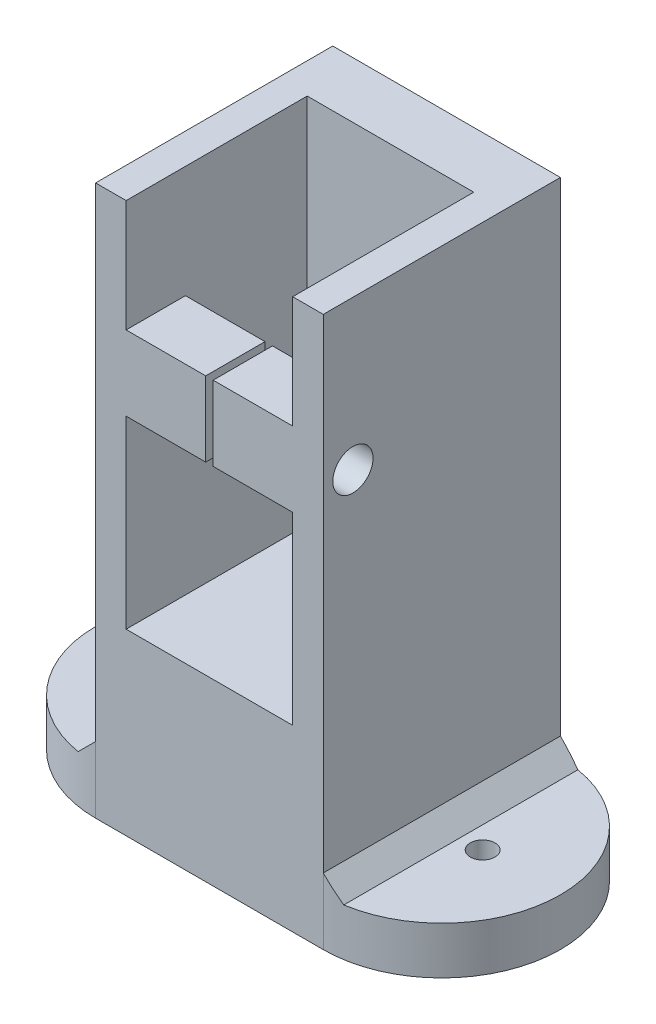
SolidWorks part; units mm, degrees
ref_plane "Front Plane" through (0, 0, 0) normal (0, 0, 1) x (1, 0, 0)
ref_plane "Top Plane" through (0, 0, 0) normal (0, 1, 0) x (1, 0, 0)
ref_plane "Right Plane" through (0, 0, 0) normal (1, 0, 0) x (0, 0, -1)
sketch "Sketch1" plane through (0, 0, 0) normal (0, 1, 0) x (1, 0, 0)
  line L0 (-5.461, 15.875) -> (35.941, 15.875) construction
  line L1 (0, 0) -> (30.48, 0)
  line L2 (0, 0) -> (0, 31.75)
  line L3 (0, 31.75) -> (30.48, 31.75)
  line L4 (30.48, 0) -> (30.48, 31.75)
  line L6 (15.24, 31.75) -> (15.24, 0) construction
  arc A0 (0, 0) -> (0, 31.75) centre (0, 15.875) cw
  arc A1 (30.48, 0) -> (30.48, 31.75) centre (30.48, 15.875) ccw
  circle A2 centre (35.941, 15.875) radius 1.651
  circle A3 centre (-5.461, 15.875) radius 1.651
  point P7 (15.24, 15.875)
  point P9 (15.24, 15.875)
  dimension "D1" = 30.48
  dimension "D3" = 3.302
  dimension "D2" = 31.75
  dimension "D4" = 41.402
extrude "Boss-Extrude1" add sketch "Sketch1" along normal blind 6.35 contours A0 L2 A3 | L4 A1 A2 region at (-15.52, 0, -15.875) region at (30.835, 0, -15.875)
extrude "Boss-Extrude2" add sketch "Sketch1<3>" along normal blind 73.66 contours L1 L4 L3 L2 region at (15.24, 0, -15.875)
sketch "Sketch1<3>" plane through (0, 0, 0) normal (0, 1, 0) x (1, 0, 0) same geometry as "Sketch1"
sketch "Sketch2" plane through (0, 0, 0) normal (0, 0, 1) x (1, 0, 0)
  line L0 (0, 73.66) -> (30.48, 73.66) construction
  line L1 (4.09, 73.66) -> (26.39, 73.66)
  line L2 (4.09, 73.66) -> (4.09, 23.96)
  line L3 (4.09, 23.96) -> (26.39, 23.96)
  line L4 (26.39, 73.66) -> (26.39, 23.96)
  line L5 (4.09, 73.66) -> (0, 73.66) construction
  line L6 (26.39, 73.66) -> (30.48, 73.66) construction
  dimension "D1" = 22.3
  dimension "D2" = 49.7
extrude "Cut-Extrude1" cut sketch "Sketch2" against normal blind 24.24
sketch "Sketch3" plane through (0, 0, -24.24) normal (0, 0, 1) x (1, 0, 0)
  line L0 (4.09, 23.96) -> (26.39, 23.96) construction
  circle A0 centre (15.24, 28.37) radius 2.9909
  point P2 (15.24, 23.96)
  dimension "D1" = 5.9817
  dimension "D2" = 4.41
extrude "Cut-Extrude2" cut sketch "Sketch3" against normal blind 10.16
chamfer "Chamfer1" distance 2.54 angle 45 2 edges at (30.48, 6.35, -15.875) (0, 6.35, -15.875)
ref_plane "Plane1" through (15.24, 0, 0) normal (1, 0, 0) x (0, 0, -1)
sketch "Sketch4" plane through (4.09, 0, 0) normal (1, 0, 0) x (0, 0, -1)
  line L0 (0, 73.66) -> (0, 23.96) construction
  line L1 (0, 58.66) -> (7.94, 58.66)
  line L2 (0, 58.66) -> (0, 48.66)
  line L3 (0, 48.66) -> (7.94, 48.66)
  line L4 (7.94, 58.66) -> (7.94, 48.66)
  line L5 (24.24, 73.66) -> (0, 73.66) construction
  dimension "D1" = 7.94
  dimension "D2" = 10
  dimension "D3" = 15
extrude "Boss-Extrude3" add sketch "Sketch4" along normal offset from surface (10.65 mm away) 0.5 up to plane "Plane1"
mirror "Mirror1" about plane through (15.24, 0, 0) normal (1, 0, 0) of "Boss-Extrude3"
sketch "Sketch6" plane through (14.74, 0, 0) normal (1, 0, 0) x (0, 0, -1)
  line L0 (3.97, 58.66) -> (3.97, 48.66) construction
  line L1 (7.94, 58.66) -> (0, 58.66) construction
  line L2 (0, 48.66) -> (7.94, 48.66) construction
  line L3 (0, 53.66) -> (7.94, 53.66) construction
  line L4 (0, 58.66) -> (0, 48.66) construction
  line L5 (7.94, 48.66) -> (7.94, 58.66) construction
  circle A0 centre (3.97, 53.66) radius 2.6948
  dimension "D1" = 5.3895
extrude "Cut-Extrude3" cut sketch "Sketch6" against normal through all and the other way through all from surface starting at plane "Plane1"
